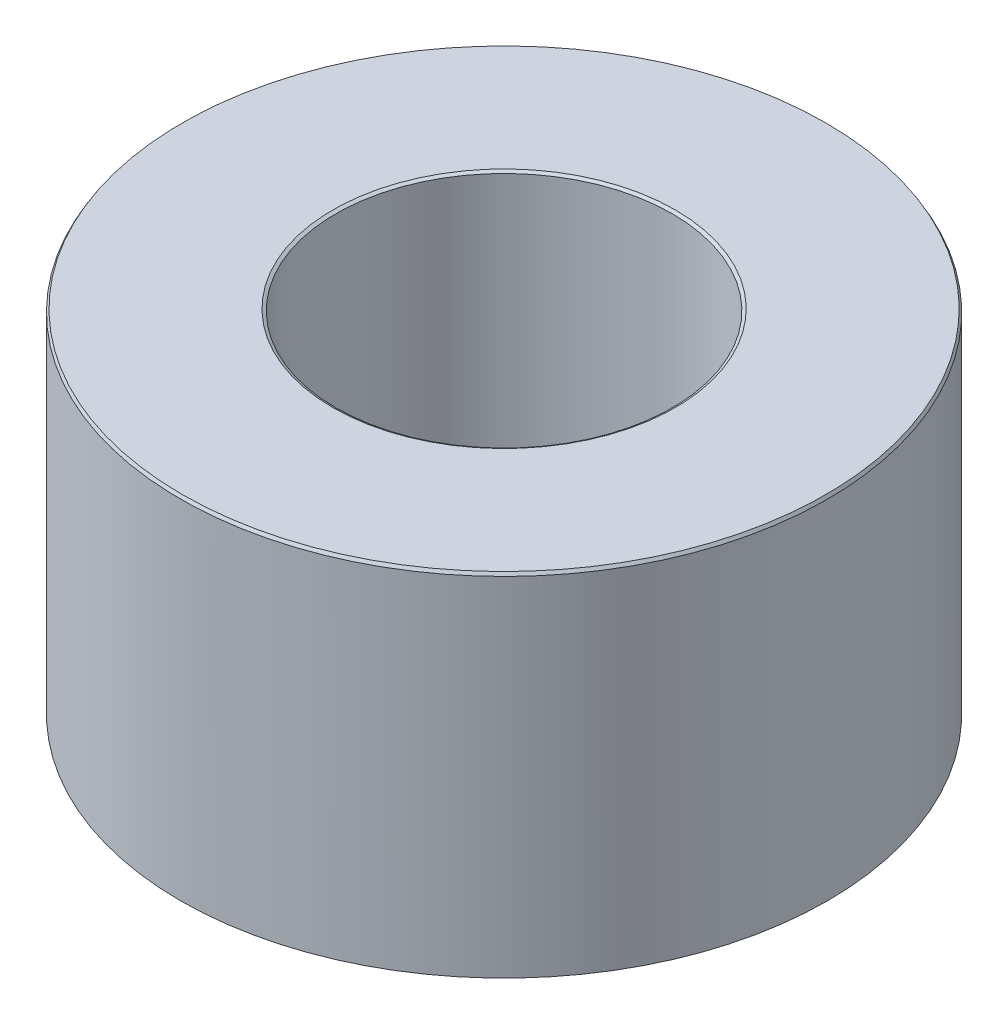
SolidWorks part; units mm, degrees
ref_plane "Front Plane" through (0, 0, 0) normal (0, 0, 1) x (1, 0, 0)
ref_plane "Top Plane" through (0, 0, 0) normal (0, 1, 0) x (1, 0, 0)
ref_plane "Right Plane" through (0, 0, 0) normal (1, 0, 0) x (0, 0, -1)
sketch "Sketch1" plane through (0, 0, 0) normal (0, 1, 0) x (1, 0, 0)
  circle A0 centre (0, 0) radius 22.5
  dimension "SLEEVE_OD" = 45
extrude "Boss-Extrude1" add sketch "Sketch1" along normal blind 24.5219
sketch "Sketch2" plane through (0, 0, 0) normal (0, 1, 0) x (1, 0, 0)
  circle A0 centre (0, 0) radius 11.6937
  dimension "BORE_D" = 23.3873
extrude "Cut-Extrude1" cut sketch "Sketch2" along normal through all
chamfer "Chamfer1" distance 0.2119 angle 30 4 edges at (0, 24.5219, 11.6937) (0, 0, 11.6937) (0, 0, 22.5) (0, 24.5219, 22.5) first distance on face at (0, 24.5219, 11.6937) first distance on face at (0, 0, 11.6937) first distance on face at (0, 24.5219, 22.5)
